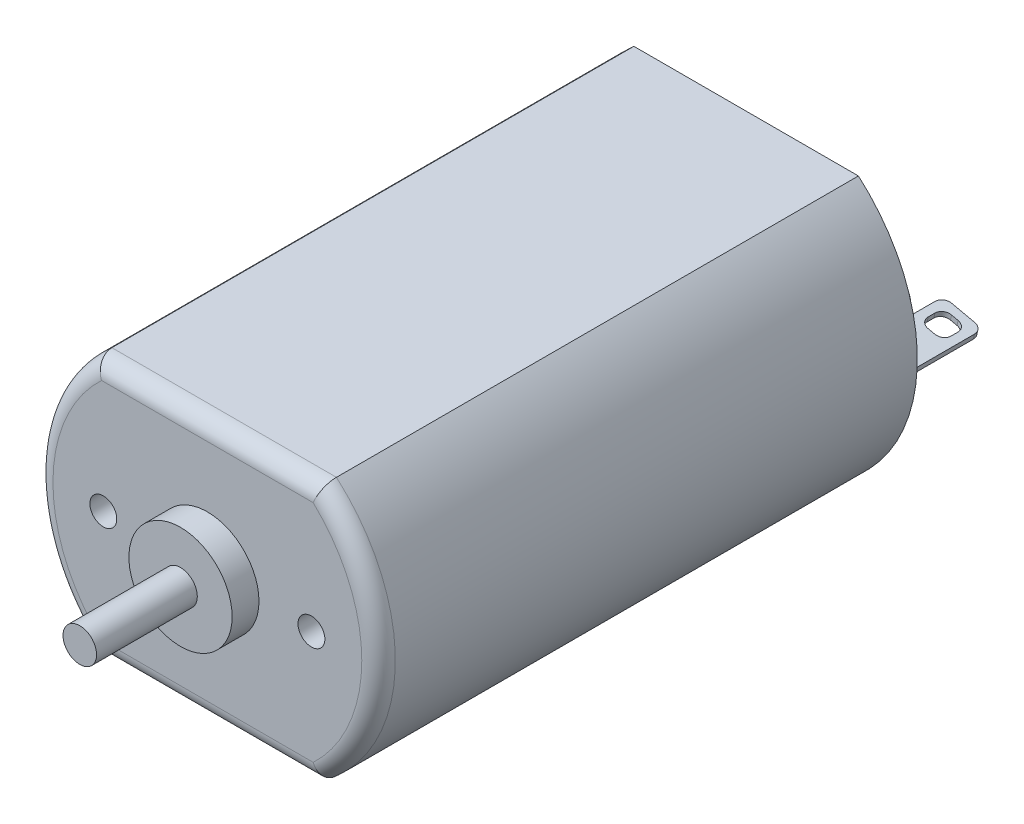
SolidWorks part; units mm, degrees
ref_plane "Front Plane" through (0, 0, 0) normal (0, 0, 1) x (1, 0, 0)
ref_plane "Top Plane" through (0, 0, 0) normal (0, 1, 0) x (1, 0, 0)
ref_plane "Right Plane" through (0, 0, 0) normal (1, 0, 0) x (0, 0, -1)
sketch "Sketch1" plane through (0, 0, 0) normal (0, 0, 1) x (1, 0, 0)
  line L0 (-6.6895, 7.7) -> (6.6895, 7.7)
  line L1 (-6.6895, -7.7) -> (6.6895, -7.7)
  arc A0 (-6.6895, 7.7) -> (-6.6895, -7.7) centre (0, 0) ccw
  arc A1 (6.6895, -7.7) -> (6.6895, 7.7) centre (0, 0) ccw
  dimension "D1" = 20.4
  dimension "D2" = 15.4
  dimension "D3" = 7.7
extrude "Boss-Extrude1" add sketch "Sketch1" along normal blind 32.1
sketch "Sketch2" plane through (0, 0, 32.1) normal (0, 0, 1) x (1, 0, 0)
  circle A0 centre (0, 0) radius 3.075
  dimension "D1" = 6.15
extrude "Boss-Extrude2" add sketch "Sketch2" along normal blind 1.6
sketch "Sketch3" plane through (0, 0, 0) normal (0, 0, -1) x (-1, 0, 0)
  circle A0 centre (0, 0) radius 3.075
  dimension "D1" = 6.15
extrude "Boss-Extrude3" add sketch "Sketch3" along normal blind 2.1
hole_wizard "M2 Tapped Hole1" positions "Sketch4" profile "Sketch5" tap size "M2" standard "ISO"
sketch "Sketch4" plane through (0, 0, 32.1) normal (0, 0, 1) x (1, 0, 0)
  line L0 (-6.2, 0) -> (6.2, 0) construction
  point P0 (-6.2, 0)
  point P2 (6.2, 0)
  dimension "D1" = 6.2
  dimension "D2" = 12.4
sketch "Sketch5" plane through (-6.2, 0, 32.1) normal (1, 0, 0) x (0, -1, 0)
  line L0 (0, 0) -> (0, 6.4807)
  line L1 (0, 6.4807) -> (0.8, 6)
  line L2 (0.8, 6) -> (0.8, 0)
  line L5 (0.8, 0) -> (0, 0)
  line L10 (0, 6.4807) -> (-0.8, 6) construction
  line L11 (0, -6.35) -> (0, 107.95) construction
  dimension "Tap Drill Dia." = 1.6
  dimension "Tap Drill Depth" = 6
  dimension "Drill Angle" = 118
cosmetic thread "Hole Thread1" parameters "D1"=4, "D2"=2
cosmetic thread "Hole Thread2" parameters "D1"=4, "D2"=2
sketch "Sketch6" plane through (0, 0, 0) normal (0, 0, -1) x (-1, 0, 0)
  line L0 (-7.6, 0) -> (7.6, 0) construction
  line L1 (-7.6, 1.69) -> (-7.6, -1.69) construction
  line L2 (7.6, -1.69) -> (7.6, 1.69) construction
  line L3 (-7.6, -1.69) -> (7.6, 1.69) construction
  circle A0 centre (-7.6, 1.69) radius 1.2
  circle A1 centre (7.6, -1.69) radius 1.2
  circle A2 centre (-7.6, -1.69) radius 1.5
  circle A3 centre (7.6, 1.69) radius 1.5
  point P12 (-7.6, 0)
  point P13 (7.6, 0)
  dimension "D1" = 15.2
  dimension "D3" = 2.4
  dimension "D4" = 2.4
  dimension "D5" = 3
  dimension "D2" = 3.38
extrude "Boss-Extrude4" add sketch "Sketch6" along normal blind 1
sketch "Sketch7" plane through (0, 0, 33.7) normal (0, 0, 1) x (1, 0, 0)
  circle A0 centre (0, 0) radius 1
  dimension "D1" = 2
extrude "Boss-Extrude5" add sketch "Sketch7" along normal blind 6
fillet "Fillet1" radius 1 4 edges at (0, -7.7, 32.1) (10.2, 0, 32.1) (0, 7.7, 32.1) (-10.2, 0, 32.1)
fillet "Fillet2" radius 0.5 2 edges at (-3.075, 0, 0) (-3.075, 0, -2.1)
ref_plane "Plane1" through (0, 0, 0) normal (-0.2171, -0.9762, 0) x (-0.9762, 0.2171, 0)
sketch "Sketch9" plane through (0, 0, 0) normal (-0.2171, -0.9762, 0) x (-0.9762, 0.2171, 0)
  line L0 (-7.7856, 1) -> (-7.7856, 5.3) construction
  line L1 (-6.2856, 1) -> (-9.2856, 1) construction
  line L2 (0, 2.1) -> (0, 7.3455) construction
  line L3 (2.575, 2.1) -> (-2.575, 2.1) construction
  line L4 (-8.9856, 1) -> (-6.5856, 1)
  line L5 (-6.5856, 1) -> (-6.5856, 4.8)
  line L6 (-7.0856, 5.3) -> (-8.4856, 5.3)
  line L7 (-8.9856, 4.8) -> (-8.9856, 1)
  line L8 (-8.4856, 4.8) -> (-7.0856, 4.8)
  line L9 (-7.0856, 4.8) -> (-7.0856, 3.4)
  line L10 (-7.0856, 3.4) -> (-8.4856, 3.4)
  line L11 (-8.4856, 3.4) -> (-8.4856, 4.8)
  line L12 (7.7856, 1) -> (7.7856, 5.3) construction
  line L13 (8.9856, 1) -> (6.5856, 1)
  line L14 (6.5856, 1) -> (6.5856, 4.8)
  line L15 (8.9856, 4.8) -> (8.9856, 1)
  line L16 (8.4856, 3.4) -> (8.4856, 4.8)
  line L17 (7.0856, 3.4) -> (8.4856, 3.4)
  line L18 (7.0856, 4.8) -> (7.0856, 3.4)
  line L19 (8.4856, 4.8) -> (7.0856, 4.8)
  line L20 (7.0856, 5.3) -> (8.4856, 5.3)
  arc A0 (-6.5856, 4.8) -> (-7.0856, 5.3) centre (-7.0856, 4.8) ccw
  arc A1 (-8.4856, 5.3) -> (-8.9856, 4.8) centre (-8.4856, 4.8) ccw
  arc A2 (8.4856, 5.3) -> (8.9856, 4.8) centre (8.4856, 4.8) cw
  arc A3 (6.5856, 4.8) -> (7.0856, 5.3) centre (7.0856, 4.8) cw
  dimension "D1" = 2.4
  dimension "D2" = 1.4
  dimension "D3" = 4.3
extrude "Boss-Extrude6" add sketch "Sketch9" along normal blind 0.15 and the other way blind 0.15
fillet "Fillet3" radius 0.5 8 edges at (-6.9167, 1.5381, -3.4) (-6.9167, 1.5381, -4.8) (-8.2833, 1.8419, -4.8) (-8.2833, 1.8419, -3.4) (8.2833, -1.8419, -3.4) (8.2833, -1.8419, -4.8) (6.9167, -1.5381, -4.8) (6.9167, -1.5381, -3.4)
